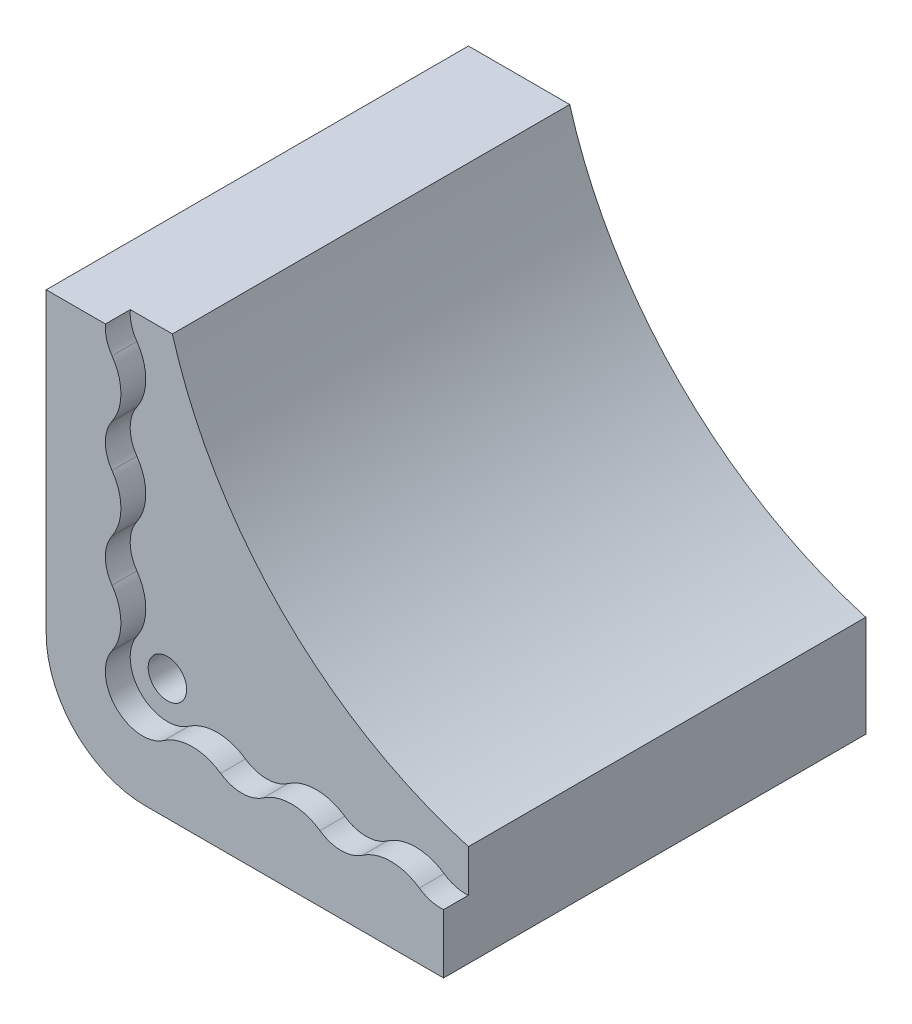
SolidWorks part; units mm, degrees
material "POM Acetal Copolymer"
ref_plane "Front Plane" through (0, 0, 0) normal (0, 0, 1) x (1, 0, 0)
ref_plane "Top Plane" through (0, 0, 0) normal (0, 1, 0) x (1, 0, 0)
ref_plane "Right Plane" through (0, 0, 0) normal (1, 0, 0) x (0, 0, -1)
sketch "Sketch1" plane through (0, 0, 0) normal (0, 0, 1) x (1, 0, 0)
  line L0 (0, 0) -> (50.8, 0)
  line L1 (50.8, 0) -> (50.8, 25.4)
  line L2 (50.8, 25.4) -> (25.4, 25.4)
  line L3 (25.4, 25.4) -> (25.4, 50.8)
  line L4 (25.4, 50.8) -> (0, 50.8)
  line L5 (0, 50.8) -> (0, 0)
  dimension "D1" = 25.4
  dimension "D2" = 25.4
extrude "Boss-Extrude1" add sketch "Sketch1" along normal blind 53.975
hole_wizard "#10 (0.1935) Diameter Hole1" positions "3DSketch1" profile "Sketch3" hole size "#10" standard "ANSI Inch" end condition up to next
sketch3d "3DSketch1"
  line L2 (0, 12.319, 53.975) -> (12.319, 12.319, 53.975) construction
  line L3 (0, 50.8, 53.975) -> (0, 0, 53.975) construction
  line L4 (12.319, 12.319, 53.975) -> (12.319, 0, 53.975) construction
  line L5 (0, 0, 53.975) -> (50.8, 0, 53.975) construction
  point P0 (12.319, 12.319, 53.975)
  dimension "D1" = 12.319
sketch "Sketch3" plane through (12.319, 12.319, 53.975) normal (1, 0, 0) x (0, -1, 0)
  line L0 (0, 0) -> (0, 53.975)
  line L1 (0, 53.975) -> (2.4574, 53.975)
  line L2 (2.4574, 53.975) -> (2.4574, 0)
  line L5 (2.4574, 0) -> (0, 0)
  line L11 (0, -6.35) -> (0, 107.95) construction
  dimension "Thru Hole Dia." = 4.9149
  dimension "Thru Hole Depth" = 53.975
sketch "Sketch4" plane through (0, 0, 53.975) normal (0, 0, 1) x (1, 0, 0)
  line L2 (0, 0) -> (50.8, 0) construction
  line L3 (0, 50.8) -> (0, 0) construction
  line L4 (7.5718, 50.8) -> (0, 50.8)
  line L5 (0, 50.8) -> (0, 12.7)
  line L6 (25.4, 50.8) -> (0, 50.8) construction
  line L9 (50.8, 0) -> (50.8, 25.4) construction
  line L10 (50.8, 0) -> (12.7, 0)
  line L11 (50.8, 7.5718) -> (50.8, 0)
  arc A13 (8.4106, 15.0404) -> (15.0404, 8.4106) centre (12.319, 12.319) ccw
  arc A14 (8.4106, 15.0404) -> (8.4106, 22.2976) centre (3.1995, 18.669) ccw
  arc A15 (8.4106, 27.7404) -> (8.4106, 22.2976) centre (12.319, 25.019) ccw
  arc A16 (8.4106, 27.7404) -> (8.4106, 34.9976) centre (3.1995, 31.369) ccw
  arc A18 (8.4106, 40.4404) -> (8.4106, 34.9976) centre (12.319, 37.719) ccw
  arc A19 (8.4106, 40.4404) -> (8.4106, 47.6976) centre (3.1995, 44.069) ccw
  arc A20 (7.5718, 50.8) -> (8.4106, 47.6976) centre (12.319, 50.419) ccw
  arc A22 (0, 12.7) -> (12.7, 0) centre (12.7, 12.7) ccw
  arc A23 (22.2976, 8.4106) -> (18.669, 9.5495) centre (18.669, 3.1995) ccw
  arc A24 (18.669, 9.5495) -> (15.0404, 8.4106) centre (18.669, 3.1995) ccw
  arc A25 (22.2976, 8.4106) -> (27.7404, 8.4106) centre (25.019, 12.319) ccw
  arc A26 (31.369, 9.5495) -> (27.7404, 8.4106) centre (31.369, 3.1995) ccw
  arc A27 (34.9976, 8.4106) -> (31.369, 9.5495) centre (31.369, 3.1995) ccw
  arc A28 (34.9976, 8.4106) -> (40.4404, 8.4106) centre (37.719, 12.319) ccw
  arc A29 (44.069, 9.5495) -> (40.4404, 8.4106) centre (44.069, 3.1995) ccw
  arc A30 (47.6976, 8.4106) -> (44.069, 9.5495) centre (44.069, 3.1995) ccw
  arc A31 (47.6976, 8.4106) -> (50.8, 7.5718) centre (50.419, 12.319) ccw
  circle M3 centre (12.319, 12.319) radius 2.4574
  line M4 (0, 50.8) -> (0, 0)
  line M5 (0, 0) -> (50.8, 0)
  line M6 (50.8, 0) -> (50.8, 25.4)
  line M7 (50.8, 25.4) -> (25.4, 25.4)
  line M8 (25.4, 25.4) -> (25.4, 50.8)
  line M9 (25.4, 50.8) -> (0, 50.8)
  dimension "D1" = 12.7
  dimension "D2" = 12.7
  dimension "D3" = 12.7
extrude "Cut-Extrude2" cut sketch "Sketch4" against normal through all contours A23 M4 M5 region at (2.8368, 2.8368, 53.975)
extrude "Cut-Extrude3" cut sketch "Sketch4<4>" against normal blind 3.175 contours L4 M9 M6 M7 M8 M3 region at (25.0828, 25.0828, 53.975)
sketch "Sketch4<4>" plane through (0, 0, 53.975) normal (0, 0, 1) x (1, 0, 0) same geometry as "Sketch4"
sketch "Sketch7" plane through (0, 0, 50.8) normal (0, 0, 1) x (1, 0, 0)
  line L0 (0, 50.8) -> (0, 12.7)
  line L1 (50.8, 0) -> (12.7, 0)
  line L2 (50.8, 12.954) -> (50.8, 0)
  line L3 (0, 50.8) -> (12.954, 50.8)
  line L4 (12.954, 50.8) -> (25.4, 50.8)
  line L5 (25.4, 50.8) -> (25.4, 28.7091)
  line L6 (28.7091, 25.4) -> (50.8, 25.4)
  line L7 (50.8, 25.4) -> (50.8, 12.954)
  line L9 (25.4, 50.8) -> (7.5718, 50.8) construction
  line L13 (50.8, 25.4) -> (25.4, 25.4) construction
  line L14 (25.4, 25.4) -> (25.4, 50.8) construction
  line L15 (0, 50.8) -> (0, 12.7) construction
  line L16 (12.7, 0) -> (50.8, 0) construction
  line L17 (50.8, 0) -> (50.8, 7.5718) construction
  line L18 (25.4, 28.7091) -> (25.4, 25.4)
  line L19 (25.4, 25.4) -> (28.7091, 25.4)
  arc A0 (12.954, 50.8) -> (50.8, 12.954) centre (66.3083, 66.3083) ccw
  arc A1 (0, 12.7) -> (12.7, 0) centre (12.7, 12.7) ccw
  arc A4 (0, 12.7) -> (12.7, 0) centre (12.7, 12.7) ccw construction
  point P8 (12.7, 12.7)
  line M9 (25.4, 50.8) -> (7.5718, 50.8)
  line M21 (50.8, 7.5718) -> (50.8, 25.4)
  line M22 (50.8, 25.4) -> (25.4, 25.4)
  line M23 (25.4, 25.4) -> (25.4, 50.8)
  dimension "D1" = 55.5625
  dimension "D2" = 12.954
  dimension "D3" = 12.954
extrude "Cut-Extrude5" cut sketch "Sketch7" against normal through all contours A0 M9 M23 | A0 M22 M21 region at (20.8556, 42.8288, 50.8) region at (42.8288, 20.8556, 50.8)
sketch "Sketch8" plane through (0, 0, 50.8) normal (0, 0, 1) x (1, 0, 0)
  arc A0 (25.4, 28.7091) -> (28.7091, 25.4) centre (66.3083, 66.3083) ccw
  arc A1 (12.954, 50.8) -> (25.4, 28.7091) centre (66.3083, 66.3083) ccw construction
extrude "Extrude-Thin1" add sketch "Sketch8" against normal up to surface (50.8 mm away) thin up to face at (14.7764, 12.319, 0) thin type one direction wall 2.54
